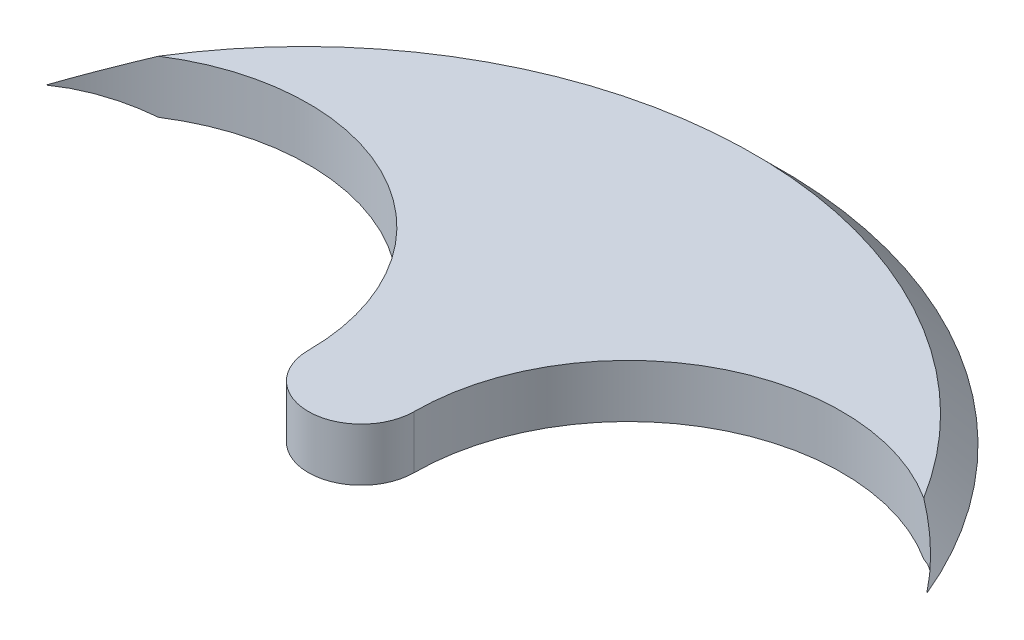
SolidWorks part; units mm, degrees
ref_plane "Front Plane" through (0, 0, 0) normal (0, 0, 1) x (1, 0, 0)
ref_plane "Top Plane" through (0, 0, 0) normal (0, 1, 0) x (1, 0, 0)
ref_plane "Right Plane" through (0, 0, 0) normal (1, 0, 0) x (0, 0, -1)
other "Configuration Table"
sketch "Sketch1" plane through (0, 0, 0) normal (0, 1, 0) x (1, 0, 0)
  line L0 (0, 18) -> (0, 0) construction
  line L1 (0, 0) -> (16.6298, 6.8883) construction
  line L2 (0, 0) -> (-16.6298, 6.8883) construction
  line L3 (-2, 2.1648) -> (2, 2.1648) construction
  arc A0 (16.6298, 6.8883) -> (-16.6298, 6.8883) centre (0, 0) ccw
  arc A1 (-2, 2.1648) -> (2, 2.1648) centre (0, 2.1648) ccw
  arc A2 (16.6298, 6.8883) -> (2, 2.1648) centre (10.0775, 2.1648) ccw
  arc A3 (-16.6298, 6.8883) -> (-2, 2.1648) centre (-10.0775, 2.1648) cw
  dimension "D1" = 18
  dimension "D3" = 4
  dimension "D2" = 135
extrude "Boss-Extrude1" add sketch "Sketch1" along normal mid plane 2
chamfer "Chamfer1" distance 1 angle 45 2 edges at (0, -1, -18) (0, 1, -18)
